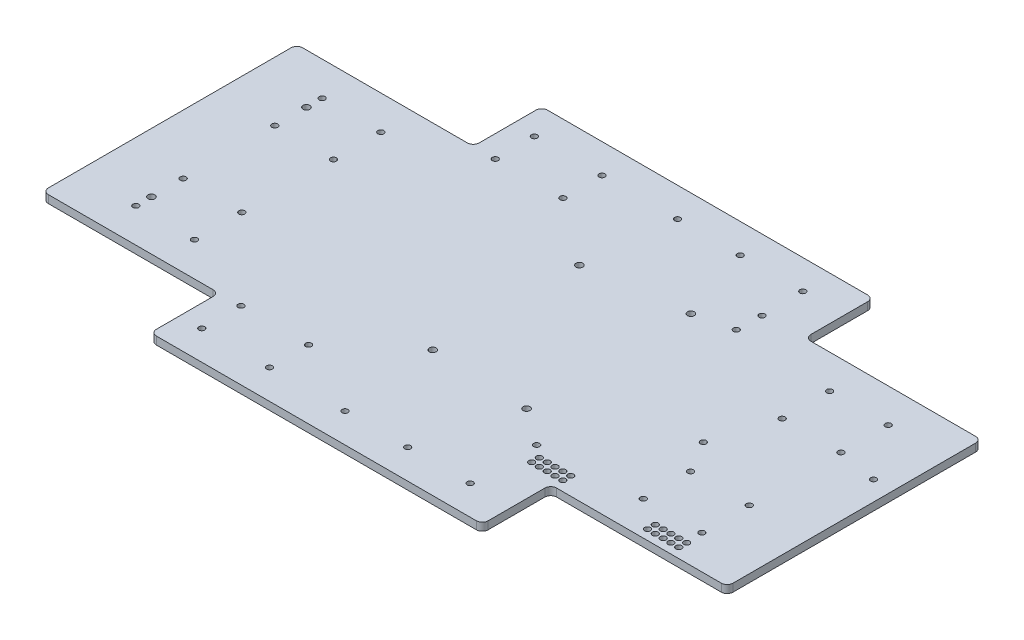
SolidWorks part; units mm, degrees
ref_plane "前视基准面" through (0, 0, 0) normal (0, 0, 1) x (1, 0, 0)
ref_plane "上视基准面" through (0, 0, 0) normal (0, 1, 0) x (1, 0, 0)
ref_plane "右视基准面" through (0, 0, 0) normal (1, 0, 0) x (0, 0, -1)
sketch "草图1" plane through (0, 0, 0) normal (0, 1, 0) x (1, 0, 0)
  line L9 (159.6457, 129.4766) -> (119.4457, 129.4766) construction
  line L14 (-140.3543, 129.4766) -> (-100.1543, 129.4766) construction
  line L17 (159.6457, -0.5234) -> (119.4457, -0.5234) construction
  line L20 (-140.3543, -0.5234) -> (-100.1543, -0.5234) construction
  line L24 (-165.3543, -0.5234) -> (-165.3543, 129.4766)
  line L25 (-165.3543, 129.4766) -> (-75.1543, 129.4766)
  line L26 (-75.1543, 129.4766) -> (-75.1543, 164.4766)
  line L27 (-75.1543, 164.4766) -> (94.4457, 164.4766)
  line L28 (94.4457, 164.4766) -> (94.4457, 129.4766)
  line L29 (94.4457, 129.4766) -> (184.6457, 129.4766)
  line L30 (184.6457, 129.4766) -> (184.6457, -0.5234)
  line L31 (184.6457, -0.5234) -> (94.4457, -0.5234)
  line L32 (94.4457, -0.5234) -> (94.4457, -35.5234)
  line L33 (94.4457, -35.5234) -> (-75.1543, -35.5234)
  line L34 (-75.1543, -35.5234) -> (-75.1543, -0.5234)
  line L35 (-75.1543, -0.5234) -> (-165.3543, -0.5234)
  circle A14 centre (-135.0604, 24.8558) radius 1.75
  circle A42 centre (-135.0604, 104.0973) radius 1.75
  circle A54 centre (-105.0604, 87.8973) radius 1.5
  circle A55 centre (-105.0604, 112.0973) radius 1.5
  circle A56 centre (-135.0604, 87.8973) radius 1.5
  circle A57 centre (-135.0604, 112.0973) radius 1.5
  circle A58 centre (-105.0604, 41.0558) radius 1.5
  circle A59 centre (-135.0604, 41.0558) radius 1.5
  circle A60 centre (-105.0604, 16.8558) radius 1.5
  circle A61 centre (-135.0604, 16.8558) radius 1.5
  circle A62 centre (124.3517, 16.8558) radius 1.5
  circle A63 centre (154.3517, 16.8558) radius 1.5
  circle A64 centre (124.3517, 41.0558) radius 1.5
  circle A65 centre (154.3517, 41.0558) radius 1.5
  circle A66 centre (124.3517, 87.8973) radius 1.5
  circle A67 centre (154.3517, 87.8973) radius 1.5
  circle A68 centre (124.3517, 112.0973) radius 1.5
  circle A69 centre (154.3517, 112.0973) radius 1.5
  point P23 (154.3517, 79.8973)
  point P42 (159.6457, 64.4766)
  dimension "D1" = 3
  dimension "D3" = 3
  dimension "D4" = 3
  dimension "D5" = 3
  dimension "D2" = 24.2
extrude "凸台-拉伸1" add sketch "草图1" along normal blind 4
sketch "草图2" plane through (0, 4, 0) normal (0, 1, 0) x (1, 0, 0)
  line L0 (-21.6362, 154.4766) -> (-21.6362, -25.5234)
  line L1 (-21.6362, 154.4766) -> (-71.6362, 154.4766)
  line L2 (-71.6362, 154.4766) -> (-71.6362, -25.5234)
  line L3 (-21.6362, -25.5234) -> (-71.6362, -25.5234)
  line L4 (-75.1543, 129.4766) -> (-75.1543, -0.5234)
  line L5 (-75.1543, 64.4766) -> (196.6659, 64.4766)
  line L6 (-71.6362, 64.4766) -> (0.5036, 64.4766)
  circle A0 centre (-29.3502, 149.4766) radius 1.5
  circle A1 centre (-29.3502, 129.4766) radius 1.5
  circle A2 centre (-63.9223, 149.4766) radius 1.5
  circle A3 centre (-63.9223, 129.4766) radius 1.5
  circle A4 centre (-29.3502, -0.5234) radius 1.5
  circle A5 centre (-29.3502, -20.5234) radius 1.5
  circle A6 centre (-63.9223, -20.5234) radius 1.5
  circle A7 centre (-63.9223, -0.5234) radius 1.5
  circle A8 centre (9.2885, 149.4766) radius 1.5
  circle A9 centre (41.2885, 149.4766) radius 1.5
  circle A10 centre (73.2885, 149.4766) radius 1.5
  circle A13 centre (73.2885, 115.5083) radius 1.5
  circle A16 centre (41.2885, -20.5234) radius 1.5
  circle A17 centre (73.2885, -20.5234) radius 1.5
  circle A18 centre (73.2885, 13.4448) radius 1.5
  circle A21 centre (9.2885, -20.5234) radius 1.5
  point P40 (9.2885, -20.5234)
  dimension "D1" = 32
  dimension "D2" = 32
extrude "切除-拉伸1" cut sketch "草图2" against normal through all contours A2 | A3 | A1 | A0 | A8 | A9 | A10 | A13 | A18 | A17 | A16 | A7 | A4 | A5 | A6 | A21
fillet "圆角1" radius 3 1 edges at (-75.1543, 2, -164.4766) type face fillet first side face at (-75.1543, 2, -146.9766) second side face at (9.6457, 2, -164.4766)
fillet "圆角2" radius 3 1 edges at (-165.3543, 2, -129.4766) type face fillet first side face at (-120.2543, 2, -129.4766) first side face at (-75.1543, 2, -145.4766) second side face at (-165.3543, 2, -64.4766)
fillet "圆角3" radius 3 1 edges at (-75.1543, 2, -129.4766) type face fillet first side face at (-75.1543, 2, -145.4766) second side face at (-118.7543, 2, -129.4766)
fillet "圆角4" radius 3 1 edges at (-165.3543, 2, 0.5234) type face fillet first side face at (-165.3543, 2, -62.9766) second side face at (-120.2543, 2, 0.5234)
fillet "圆角5" radius 3 1 edges at (-75.1543, 2, 0.5234) type face fillet first side face at (-75.1543, 2, 18.0234) second side face at (-118.7543, 2, 0.5234)
fillet "圆角6" radius 3 1 edges at (-75.1543, 2, 35.5234) type face fillet first side face at (-75.1543, 2, 19.5234) second side face at (9.6457, 2, 35.5234)
fillet "圆角7" radius 3 1 edges at (94.4457, 2, 35.5234) type face fillet first side face at (94.4457, 2, 18.0234) second side face at (11.1457, 2, 35.5234)
fillet "圆角8" radius 3 1 edges at (94.4457, 2, 0.5234) type face fillet first side face at (139.5457, 2, 0.5234) second side face at (94.4457, 2, 16.5234)
fillet "圆角9" radius 3 1 edges at (184.6457, 2, 0.5234) type face fillet first side face at (184.6457, 2, -64.4766) second side face at (141.0457, 2, 0.5234)
fillet "圆角10" radius 3 1 edges at (184.6457, 2, -129.4766) type face fillet first side face at (139.5457, 2, -129.4766) second side face at (184.6457, 2, -65.9766)
fillet "圆角11" radius 3 1 edges at (94.4457, 2, -129.4766) type face fillet first side face at (94.4457, 2, -146.9766) second side face at (138.0457, 2, -129.4766)
fillet "圆角12" radius 3 1 edges at (94.4457, 2, -164.4766) type face fillet first side face at (11.1457, 2, -164.4766) second side face at (94.4457, 2, -148.4766)
sketch "草图3" plane through (0, 4, 0) normal (0, 1, 0) x (1, 0, 0)
  line L0 (2.8483, 28.9766) -> (2.5983, 28.9766) construction
  line L1 (2.5983, 115.4766) -> (56.5983, 115.4766) construction
  line L2 (2.5983, 115.4766) -> (2.5983, 13.4766) construction
  line L3 (2.5983, 13.4766) -> (56.5983, 13.4766) construction
  line L4 (56.5983, 115.4766) -> (56.5983, 13.4766) construction
  line L5 (2.5983, 115.4766) -> (56.5983, 13.4766) construction
  line L6 (2.5983, 13.4766) -> (56.5983, 115.4766) construction
  line L7 (56.3483, 26.9766) -> (56.5983, 26.9766) construction
  line L8 (4.5983, 103.9766) -> (4.5983, 28.9766) construction
  line L9 (54.5983, 110.9766) -> (54.5983, 26.9766) construction
  circle A0 centre (54.5983, 26.9766) radius 1.75
  circle A2 centre (54.5983, 110.9766) radius 1.75
  circle A3 centre (4.5983, 28.9766) radius 1.75
  circle A4 centre (4.5983, 103.9766) radius 1.75
  point P0 (29.5983, 64.4766)
  dimension "D3" = 3.5
  dimension "D6" = 3.5
  dimension "D8" = 3.5
  dimension "D11" = 3.5
  dimension "D1" = 102
  dimension "D2" = 54
  dimension "D4" = 13.5
  dimension "D5" = 2
  dimension "D7" = 4.5
  dimension "D9" = 15.5
  dimension "D10" = 2
  dimension "D12" = 75
extrude "切除-拉伸2" cut sketch "草图3" against normal through all
sketch "草图5" plane through (0, 4, 0) normal (0, 1, 0) x (1, 0, 0)
  line L0 (184.6457, 2.4766) -> (184.6457, 126.4766) construction
  line L1 (91.4457, 164.4766) -> (-72.1543, 164.4766) construction
  circle A0 centre (73.6457, 128.2966) radius 1.5
  circle A1 centre (174.6457, 84.2966) radius 1.5
  circle A2 centre (114.6457, 57.2966) radius 1.5
  dimension "D1" = 3
  dimension "D3" = 36.18
  dimension "D4" = 3
  dimension "D5" = 10
  dimension "D6" = 80.18
  dimension "D7" = 3
  dimension "D8" = 70
  dimension "D9" = 107.18
  dimension "D2" = 111
extrude "切除-拉伸3" cut sketch "草图5" against normal through all
sketch "草图6" plane through (0, 4, 0) normal (0, 1, 0) x (1, 0, 0)
  line L0 (91.4457, 164.4766) -> (-72.1543, 164.4766) construction
  line L1 (87.6357, 8.4866) -> (184.6457, 8.4866) construction
  line L2 (184.6457, 2.4766) -> (184.6457, 126.4766) construction
  line L3 (87.6357, 8.4866) -> (91.6357, 8.4866) construction
  circle A0 centre (87.6357, 8.4866) radius 1.5
  circle A2 centre (146.8957, 8.4866) radius 1.5
  circle A6 centre (83.6357, 8.4866) radius 1.5
  circle A9 centre (142.8957, 8.4866) radius 1.5
  circle A10 centre (79.6357, 8.4866) radius 1.5
  circle A13 centre (138.8957, 8.4866) radius 1.5
  circle A14 centre (87.6357, 8.4866) radius 1.5
  circle A17 centre (146.8957, 8.4866) radius 1.5
  circle A18 centre (83.6357, 8.4866) radius 1.5
  circle A21 centre (142.8957, 8.4866) radius 1.5
  circle A22 centre (91.6357, 8.4866) radius 1.5
  circle A25 centre (150.8957, 8.4866) radius 1.5
  circle A26 centre (87.6357, 8.4866) radius 1.5
  circle A29 centre (146.8957, 8.4866) radius 1.5
  circle A30 centre (91.6357, 8.4866) radius 1.5
  circle A33 centre (150.8957, 8.4866) radius 1.5
  circle A34 centre (95.6357, 8.4866) radius 1.5
  circle A37 centre (154.8957, 8.4866) radius 1.5
  circle A38 centre (87.6357, 4.4866) radius 1.5
  circle A41 centre (146.8957, 4.4866) radius 1.5
  circle A46 centre (79.6357, 4.4866) radius 1.5
  circle A47 centre (83.6357, 4.4866) radius 1.5
  circle A48 centre (91.6357, 4.4866) radius 1.5
  circle A49 centre (95.6357, 4.4866) radius 1.5
  circle A52 centre (138.8957, 4.4866) radius 1.5
  circle A53 centre (142.8957, 4.4866) radius 1.5
  circle A54 centre (150.8957, 4.4866) radius 1.5
  circle A55 centre (154.8957, 4.4866) radius 1.5
  dimension "D2" = 3
  dimension "D4" = 3
  dimension "D8" = 3
  dimension "D1" = 155.99
  dimension "D3" = 97.01
  dimension "D5" = 4
  dimension "D9" = 2
extrude "切除-拉伸4" cut sketch "草图6" against normal blind 10 contours A0 | A47 | A34 | A22 | A6 | A10 | A46 | A38 | A48 | A49 | A13 | A9 | A2 | A25 | A37 | A55 | A54 | A41 | A53 | A52 region at (87.6357, 4, -8.4866) region at (83.6357, 4, -4.4866)
